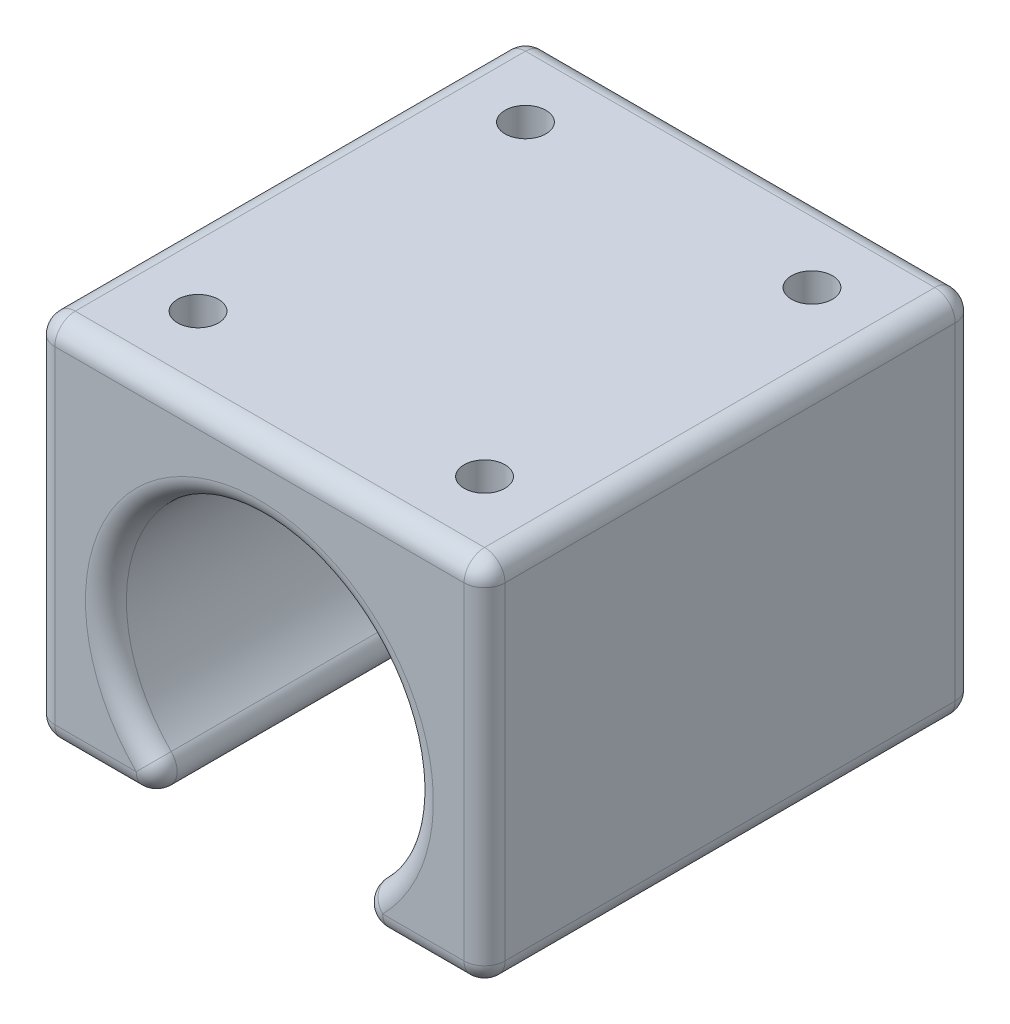
SolidWorks part; units mm, degrees
material "Alliage 1060"
ref_plane "Plan de face" through (0, 0, 0) normal (0, 0, 1) x (1, 0, 0)
ref_plane "Plan de dessus" through (0, 0, 0) normal (0, 1, 0) x (1, 0, 0)
ref_plane "Plan de droite" through (0, 0, 0) normal (1, 0, 0) x (0, 0, -1)
sketch "Esquisse1" plane through (0, 0, 0) normal (0, 0, 1) x (1, 0, 0)
  line L0 (0, 0) -> (0, -2) construction
  line L1 (11, -9) -> (2.6926, -9)
  line L2 (11, -9) -> (11, 9)
  line L3 (11, 9) -> (-11, 9)
  line L4 (-11, -9) -> (-11, 9)
  line L5 (11, -9) -> (-11, 9) construction
  line L6 (11, 9) -> (-11, -9) construction
  line L7 (2.6926, -9) -> (-2.6926, -9) construction
  line L8 (-2.6926, -9) -> (-11, -9)
  arc A1 (2.6926, -9) -> (-2.6926, -9) centre (0, -2) ccw
  arc A2 (-2.6926, -9) -> (2.6926, -9) centre (0, -2) ccw construction
  point P0 (0, 0)
  dimension "D2" = 2
  dimension "D4" = 15
  dimension "D1" = 11
  dimension "D3" = 11
extrude "Boss.-Extru.1" add sketch "Esquisse1" along normal blind 12 and the other way blind 12
sketch "Esquisse2" plane through (0, 0, 0) normal (0, 1, 0) x (1, 0, 0)
  line L0 (11, 12) -> (-11, 12) construction
  line L1 (7, -8) -> (-7, -8) construction
  line L2 (7, -8) -> (7, 8) construction
  line L3 (7, 8) -> (-7, 8) construction
  line L4 (-7, -8) -> (-7, 8) construction
  line L5 (7, -8) -> (-7, 8) construction
  line L6 (7, 8) -> (-7, -8) construction
  line L7 (-11, 12) -> (-11, -12) construction
  circle A0 centre (-7, 8) radius 1
  circle A1 centre (7, 8) radius 1
  circle A2 centre (7, -8) radius 1
  circle A3 centre (-7, -8) radius 1
  point P0 (0, 0)
  dimension "D3" = 2
  dimension "D4" = 2
  dimension "D5" = 2
  dimension "D6" = 2
  dimension "D1" = 14
  dimension "D2" = 16
extrude "Enlèv. mat.-Extru.1" cut sketch "Esquisse2" against normal blind 4 from surface starting at face at (0, 9, 0)
fillet "Congé1" radius 1 18 edges at (-11, 9, 0) (-11, -9, 0) (-6.8463, -9, -12) (0, 5.5, -12) (6.8463, -9, -12) (0, 9, -12) (-11, 0, -12) (11, 0, -12) (11, -9, 0) (11, 9, 0) (0, 9, 12) (11, 0, 12) (6.8463, -9, 12) (0, 5.5, 12) (-6.8463, -9, 12) (-11, 0, 12) (2.6926, -9, 0) (-2.6926, -9, 0)
